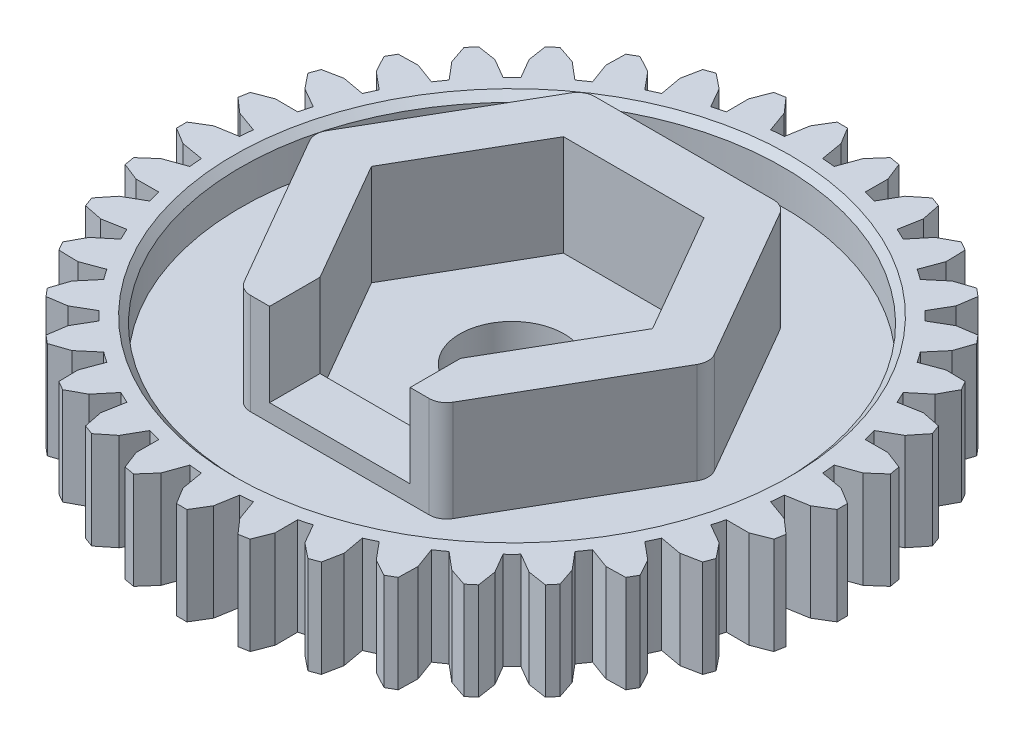
SolidWorks part; units mm, degrees
ref_plane "Front Plane" through (0, 0, 0) normal (0, 0, 1) x (1, 0, 0)
ref_plane "Top Plane" through (0, 0, 0) normal (0, 1, 0) x (1, 0, 0)
ref_plane "Right Plane" through (0, 0, 0) normal (1, 0, 0) x (0, 0, -1)
sketch "Sketch2" plane through (0, 0, 0) normal (0, 1, 0) x (1, 0, 0)
  circle A0 centre (0, 0) radius 8.4
  dimension "D1" = 16.8
extrude "Boss-Extrude1" add sketch "Sketch2" along normal blind 2.8
sketch "Sketch3" plane through (0, 2.8, 0) normal (0, 1, 0) x (1, 0, 0)
  circle A0 centre (0, 0) radius 7.8
  dimension "D1" = 15.6
extrude "Cut-Extrude1" cut sketch "Sketch3" against normal blind 1.2
chamfer "Chamfer1" distance 0.2 angle 45 1 edges at (0, 2.8, 7.8)
sketch "Sketch4" plane through (0, 1.6, 0) normal (0, 1, 0) x (1, 0, 0)
  line L0 (-5.7158, 0) -> (-4.0415, 0) construction
  line L13 (-4.0415, 0) -> (-2.0207, -3.5)
  line L14 (-2.0207, -3.5) -> (2.0207, -3.5)
  line L15 (2.0207, -3.5) -> (4.0415, 0)
  line L16 (4.0415, 0) -> (2.0207, 3.5)
  line L17 (2.0207, 3.5) -> (-2.0207, 3.5)
  line L18 (-2.0207, 3.5) -> (-4.0415, 0)
  line L19 (-5.7158, 0) -> (-2.8579, -4.95)
  line L20 (-2.8579, -4.95) -> (2.8579, -4.95)
  line L21 (2.8579, -4.95) -> (5.7158, 0)
  line L22 (5.7158, 0) -> (2.8579, 4.95)
  line L23 (2.8579, 4.95) -> (-2.8579, 4.95)
  line L24 (-2.8579, 4.95) -> (-5.7158, 0)
  line L25 (0, 0) -> (-4.0415, 0) construction
  line L26 (2.0207, -3.5) -> (2.0207, -4.95)
  line L27 (-2.0207, -3.5) -> (-2.0207, -4.95)
  circle A0 centre (0, 0) radius 4.0415 construction
  circle A1 centre (0, 0) radius 5.7158 construction
  dimension "D2" = 9.9
  dimension "D1" = 7
extrude "Boss-Extrude2" add sketch "Sketch4" along normal blind 4.5 from surface contours L27 L13 L18 L17 L16 L15 L26 L20 L21 L22 L23 L24 L19 region at (-3.1621, 1.6, 1.8256) starting at face at (0, 0, 8.4)
sketch "Sketch5" plane through (0, 1.6, 0) normal (0, 1, 0) x (1, 0, 0)
  line L0 (2.0207, -4.95) -> (2.0207, -3.5)
  line L1 (2.0207, -4.95) -> (-2.0207, -4.95)
  line L2 (2.0207, -3.5) -> (-2.0207, -3.5)
  line L3 (-2.0207, -4.95) -> (-2.0207, -3.5)
extrude "Boss-Extrude3" add sketch "Sketch5" along normal offset from surface (0.5 mm away) 2.4 up to face at (0, 4.5, 0.7071)
sketch "Sketch6" plane through (0, 1.6, 0) normal (0, 1, 0) x (1, 0, 0)
  circle A0 centre (0, 0) radius 1.5
  dimension "D1" = 3
extrude "Cut-Extrude2" cut sketch "Sketch6" against normal up to surface (1.6 mm away) up to face at (0, 0, 8.4)
sketch "Sketch8" plane through (0, 0, 0) normal (0, -1, 0) x (1, 0, 0)
  line L1 (-0.15, 9.4988) -> (0.15, 9.4988)
  line L3 (0.55, 8.382) -> (-0.55, 8.382)
  line L4 (0, 9.4988) -> (0, 8.382) construction
  line L7 (-0.55, 8.382) -> (-0.44, 9.022)
  line L8 (-0.44, 9.022) -> (-0.15, 9.4988)
  line L9 (0.15, 9.4988) -> (0.44, 9.022)
  line L10 (0.44, 9.022) -> (0.55, 8.382)
  line L11 (0.44, 9.022) -> (-0.44, 9.022) construction
  circle A0 centre (0, 0) radius 9.5 construction
  circle A1 centre (0, 0) radius 8.4 construction
  dimension "D1" = 19
  dimension "D3" = 0.3
  dimension "D4" = 1.1
  dimension "D5" = 0.88
  dimension "D6" = 0.64
extrude "Boss-Extrude4" add sketch "Sketch8" against normal up to surface (2.8 mm away) up to face at (0, 2.8, 8)
ref_axis "Axis1" through (0, 0, 0) along (0, 1, 0)
pattern_circular "CirPattern1" count 36 every 10 about axis through (0, 0, 0) along (0, 1, 0) of "Boss-Extrude4"
fillet "Fillet1" radius 0.5 6 edges at (-2.8579, 3.05, 4.95) (2.8579, 3.05, 4.95) (5.7158, 3.05, 0) (2.8579, 3.05, -4.95) (-2.8579, 3.05, -4.95) (-5.7158, 3.05, 0)
sketch "Sketch11" plane through (0, 0, 0) normal (0, -1, 0) x (1, 0, 0)
  circle A0 centre (0, 0) radius 7.8
  circle A1 centre (0, 0) radius 8
  circle A2 centre (0, 0) radius 8 construction
  circle A3 centre (0, 0) radius 7.8 construction
extrude "Boss-Extrude5" add sketch "Sketch11" along normal blind 0.1
fillet "Fillet2" radius 0.05 2 edges at (0, -0.1, -7.8) (0, -0.1, -8)
